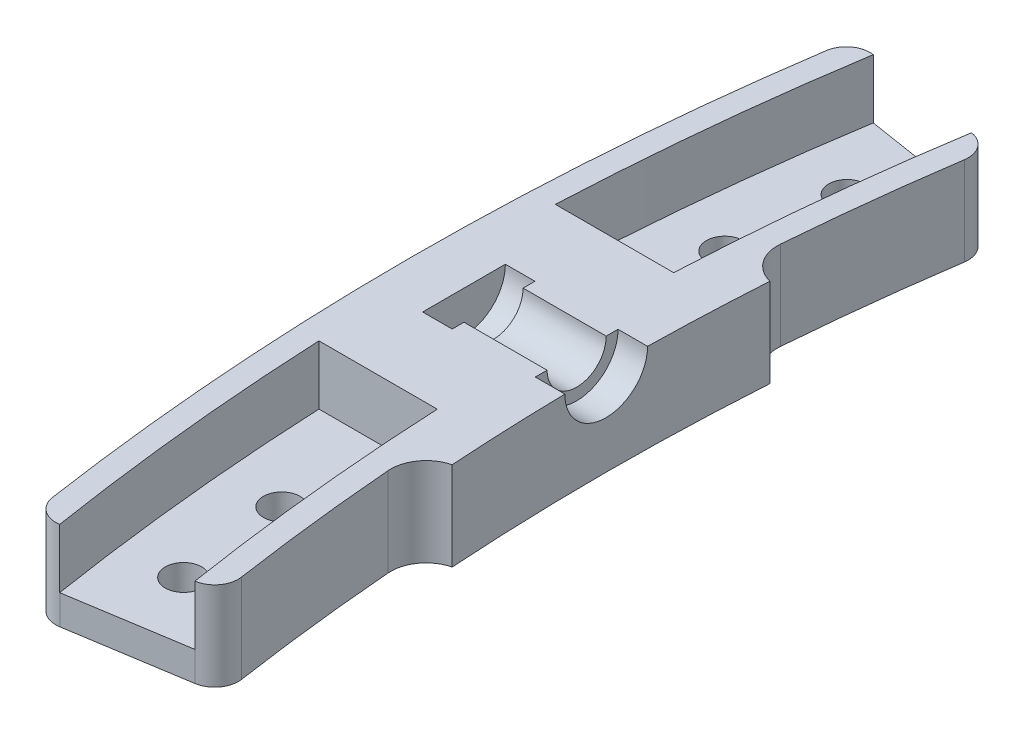
SolidWorks part; units mm, degrees
ref_plane "Front Plane" through (0, 0, 0) normal (0, 0, 1) x (1, 0, 0)
ref_plane "Top Plane" through (0, 0, 0) normal (0, 1, 0) x (1, 0, 0)
ref_plane "Right Plane" through (0, 0, 0) normal (1, 0, 0) x (0, 0, -1)
sketch "Sketch1" plane through (0, 0, 0) normal (0, 1, 0) x (1, 0, 0)
  line L0 (0, 0) -> (-217.2914, -34.4156) construction
  line L1 (0, 0) -> (-217.2914, 34.4156) construction
  line L2 (0, 0) -> (-215, 0) construction
  line L3 (-217.2914, 34.4156) -> (-207.4146, 32.8512)
  line L4 (-207.4146, -32.8512) -> (-217.2914, -34.4156)
  line L5 (0, 0) -> (-219.2668, -34.7285) construction
  line L6 (0, 0) -> (-219.2668, 34.7285) construction
  line L7 (-219.2668, 34.7285) -> (-205.4392, 32.5384)
  line L8 (-219.2668, -34.7285) -> (-205.4392, -32.5384)
  arc A0 (-217.2914, 34.4156) -> (-217.2914, -34.4156) centre (0, 0) ccw
  arc A1 (-207.4146, 32.8512) -> (-207.4146, -32.8512) centre (0, 0) ccw
  arc A2 (-212.353, -33.6334) -> (-212.353, 33.6334) centre (0, 0) cw construction
  arc A4 (-205.4392, 32.5384) -> (-205.4392, -32.5384) centre (0, 0) ccw
  arc A5 (-219.2668, 34.7285) -> (-219.2668, -34.7285) centre (0, 0) ccw
  dimension "D1" = 220
  dimension "D2" = 210
  dimension "D3" = 5
  dimension "D5" = 2
  dimension "D6" = 2
  dimension "D4" = 18
extrude "Boss-Extrude1" add sketch "Sketch1" along normal blind 10 contours A1 L3 A0 L4 | L7 A5 L8 A0 | A4 L7 A1 L8 region at (-220.0938, 0, 0) region at (-214.1555, 0, 0) region at (-208.1432, 0, 0)
ref_plane "Plane1" through (-215, 0, 0) normal (1, 0, 0) x (0, 0, -1)
sketch "Sketch15" plane through (0, 10, 0) normal (0, 1, 0) x (1, 0, 0)
  line L0 (-207.4146, -32.8512) -> (-217.2914, -34.4156) construction
  line L1 (-205, 10) -> (-225, 10)
  line L2 (-205, 10) -> (-205, -10)
  line L3 (-205, -10) -> (-225, -10)
  line L4 (-225, 10) -> (-225, -10)
  line L5 (-205, 10) -> (-225, -10) construction
  line L6 (-205, -10) -> (-225, 10) construction
  line L7 (-217.2914, 34.4156) -> (-207.4146, 32.8512) construction
  line L8 (-207.4146, -32.8512) -> (-217.2914, -34.4156)
  line L9 (-217.2914, 34.4156) -> (-207.4146, 32.8512)
  arc A2 (-207.4146, 32.8512) -> (-207.4146, -32.8512) centre (0, 0) ccw construction
  arc A3 (-217.2914, 34.4156) -> (-217.2914, -34.4156) centre (0, 0) ccw construction
  arc A4 (-207.4146, 32.8512) -> (-207.4146, -32.8512) centre (0, 0) ccw
  arc A5 (-217.2914, 34.4156) -> (-217.2914, -34.4156) centre (0, 0) ccw
  point P0 (-215, 0)
  line M5 (-219.2668, -34.7285) -> (-205.4392, -32.5384)
  line M7 (-205.4392, 32.5384) -> (-219.2668, 34.7285)
  dimension "D1" = 20
  dimension "D2" = 20
extrude "Cut-Extrude1" cut sketch "Sketch15" against normal blind 5 contours A5 L1 A4 M7 | L3 A5 A4 M5 region at (-213.8328, 10, -21.8433) region at (-213.8328, 10, 21.8433)
ref_plane "Plane2" through (-215, 0, 0) normal (-1, 0, 0) x (0, 0, 1)
sketch "Sketch12" plane through (0, 0, 0) normal (0, 1, 0) x (1, 0, 0)
  line L0 (0, 0) -> (-214.1819, -18.7385) construction
  line L1 (0, 0) -> (-213.1606, -28.0631) construction
  line L2 (0, 0) -> (-215, 0) construction
  line L3 (0, 0) -> (-215, 0) construction
  line L4 (0, 0) -> (-214.1819, 18.7385) construction
  line L5 (0, 0) -> (-213.1606, 28.0631) construction
  arc A0 (-212.353, 33.6334) -> (-212.353, -33.6334) centre (0, 0) ccw construction
  dimension "D1" = 10
  dimension "D2" = 15
hole_wizard "Ø3.1 (3.1) Diameter Hole2" positions "Sketch18" profile "Sketch17" hole size "Ø3.1" standard "ISO" end condition through all
sketch "Sketch18" plane through (0, 0, 0) normal (0, -1, 0) x (-1, 0, 0)
  point P0 (213.1606, -28.0631)
  point P3 (214.1819, -18.7385)
  point P6 (214.1819, 18.7385)
  point P9 (213.1606, 28.0631)
sketch "Sketch17" plane through (-213.1606, 0, 28.0631) normal (1, 0, 0) x (0, 0, -1)
  line L0 (0, 0) -> (0, 10)
  line L1 (0, 10) -> (1.55, 10)
  line L2 (1.55, 10) -> (1.55, 0)
  line L5 (1.55, 0) -> (0, 0)
  line L11 (0, -6.35) -> (0, 107.95) construction
  dimension "Thru Hole Dia." = 3.1
  dimension "Thru Hole Depth" = 10
sketch "Sketch19" plane through (0, 0, 0) normal (0, 1, 0) x (1, 0, 0)
  line L0 (0, 0) -> (-205.06, -13.4403) construction
  line L1 (0, 0) -> (-205.5, 0) construction
  line L2 (-205.06, -13.4403) -> (-207.5547, -13.6039)
  line L3 (-205.06, 13.4403) -> (-207.5547, 13.6039)
  arc A0 (-205.06, 13.4403) -> (-205.06, -13.4403) centre (0, 0) ccw
  arc A1 (-205.4392, 32.5384) -> (-205.4392, -32.5384) centre (0, 0) ccw construction
  arc A2 (-207.5547, 13.6039) -> (-207.5547, -13.6039) centre (0, 0) ccw
  dimension "D1" = 205.5
  dimension "D2" = 3.75
extrude "Boss-Extrude2" add sketch "Sketch19" along normal blind 10
fillet "Fillet1" radius 3 2 edges at (-207.5547, 5, -13.6039) (-207.5547, 5, 13.6039)
fillet "Fillet2" radius 2 4 edges at (-219.2668, 5, -34.7285) (-219.2668, 5, 34.7285) (-205.4392, 5, 32.5384) (-205.4392, 5, -32.5384)
sketch "Sketch20" plane through (0, 10, 0) normal (0, 1, 0) x (1, 0, 0)
  line L0 (0, 0) -> (-185, 0) construction
  line L1 (-185, 0) -> (-197.5, 0) construction
  dimension "D1" = 185
  dimension "D2" = 12.5
ref_plane "Plane3" through (-197.5, 0, 0) normal (1, 0, 0) x (0, 0, -1)
sketch "Sketch26" plane through (0, 0, 0) normal (0, -1, 0) x (1, 0, 0)
  line L2 (-217.2825, -34.4142) -> (-207.4051, -32.8497)
  line L3 (-207.4051, 32.8497) -> (-217.2825, 34.4142)
  line L4 (-217.2825, -34.4142) -> (-207.4051, -32.8497)
  line L5 (-207.4051, 32.8497) -> (-217.2825, 34.4142)
  arc A10 (-219.5735, 32.7337) -> (-219.5735, -32.7337) centre (0, 0) ccw
  arc A11 (-219.5735, -32.7337) -> (-217.2825, -34.4142) centre (-217.5953, -32.4388) ccw
  arc A12 (-207.4051, -32.8497) -> (-205.7397, -30.5803) centre (-207.718, -30.8744) ccw
  arc A13 (-207.337, -16.5936) -> (-205.7397, -30.5803) centre (0, 0) ccw
  arc A14 (-205.06, -13.4403) -> (-207.337, -16.5936) centre (-204.3466, -16.3543) ccw
  arc A15 (-205.06, 13.4403) -> (-205.06, -13.4403) centre (0, 0) ccw
  arc A16 (-207.337, 16.5936) -> (-205.06, 13.4403) centre (-204.3466, 16.3543) ccw
  arc A17 (-205.7397, 30.5803) -> (-207.337, 16.5936) centre (0, 0) ccw
  arc A18 (-205.7397, 30.5803) -> (-207.4051, 32.8497) centre (-207.718, 30.8744) ccw
  arc A19 (-217.2825, 34.4142) -> (-219.5735, 32.7337) centre (-217.5953, 32.4388) ccw
  arc A20 (-219.5735, 32.7337) -> (-219.5735, -32.7337) centre (0, 0) ccw
  arc A21 (-219.5735, -32.7337) -> (-217.2825, -34.4142) centre (-217.5953, -32.4388) ccw
  arc A22 (-207.4051, -32.8497) -> (-205.7397, -30.5803) centre (-207.718, -30.8744) ccw
  arc A23 (-207.337, -16.5936) -> (-205.7397, -30.5803) centre (0, 0) ccw
  arc A24 (-205.06, -13.4403) -> (-207.337, -16.5936) centre (-204.3466, -16.3543) ccw
  arc A25 (-205.06, 13.4403) -> (-205.06, -13.4403) centre (0, 0) ccw
  arc A26 (-207.337, 16.5936) -> (-205.06, 13.4403) centre (-204.3466, 16.3543) ccw
  arc A27 (-205.7397, 30.5803) -> (-207.337, 16.5936) centre (0, 0) ccw
  arc A28 (-205.7397, 30.5803) -> (-207.4051, 32.8497) centre (-207.718, 30.8744) ccw
  arc A29 (-217.2825, 34.4142) -> (-219.5735, 32.7337) centre (-217.5953, 32.4388) ccw
  dimension "D1" = 0
extrude "Cut-Extrude6" cut sketch "Sketch26" against normal blind 2.5
sketch "Sketch27" plane through (0, 0, 0) normal (0, 1, 0) x (1, 0, 0)
  line L0 (0, 0) -> (-205, 0) construction
  line L1 (0, 0) -> (-215, 0) construction
  line L2 (-205, 0) -> (-217.5, 0) construction
  arc A0 (-205.06, 13.4403) -> (-205.06, -13.4403) centre (0, 0) ccw construction
  point P5 (-205.5, 0)
  dimension "D1" = 205
  dimension "D2" = 12.5
ref_plane "Plane4" through (-217.5, 0, 0) normal (1, 0, 0) x (0, 0, -1)
sketch "Sketch28" plane through (-217.5, 0, 0) normal (1, 0, 0) x (0, 0, -1)
  line L0 (13.4403, 10) -> (-13.4403, 10) construction
  circle A0 centre (0, 10) radius 3.5
  dimension "D1" = 7
extrude "Cut-Extrude7" cut sketch "Sketch28" along normal blind 2.5
sketch "Sketch29" plane through (0, 10, 0) normal (0, 1, 0) x (1, 0, 0)
  line L0 (-205, 0) -> (-217.5, 0) construction
  line L1 (-207.9702, 0) -> (-205.4702, 0)
  line L2 (-207.9702, 0) -> (-207.9702, -3.5)
  line L3 (-207.9702, -3.5) -> (-205.4702, -3.5)
  line L4 (-205.4702, 0) -> (-205.4702, -3.5)
  line L6 (-217.5, 0) -> (-205, 0) construction
  arc A0 (-205.06, 13.4403) -> (-205.06, -13.4403) centre (0, 0) ccw construction
  dimension "D1" = 2.5
  dimension "D2" = 7
revolve "Cut-Revolve1" cut sketch "Sketch29" angle 360 about L6
sketch "Sketch30" plane through (-207.9702, 0, 0) normal (1, 0, 0) x (0, 0, -1)
  line L0 (3.5, 10) -> (-3.5, 10) construction
  circle A0 centre (0, 10) radius 2.5
  dimension "D1" = 5
extrude "Cut-Extrude8" cut sketch "Sketch30" against normal up to surface (7.0298 mm away) up to face at (-215, 8.25, 0)
